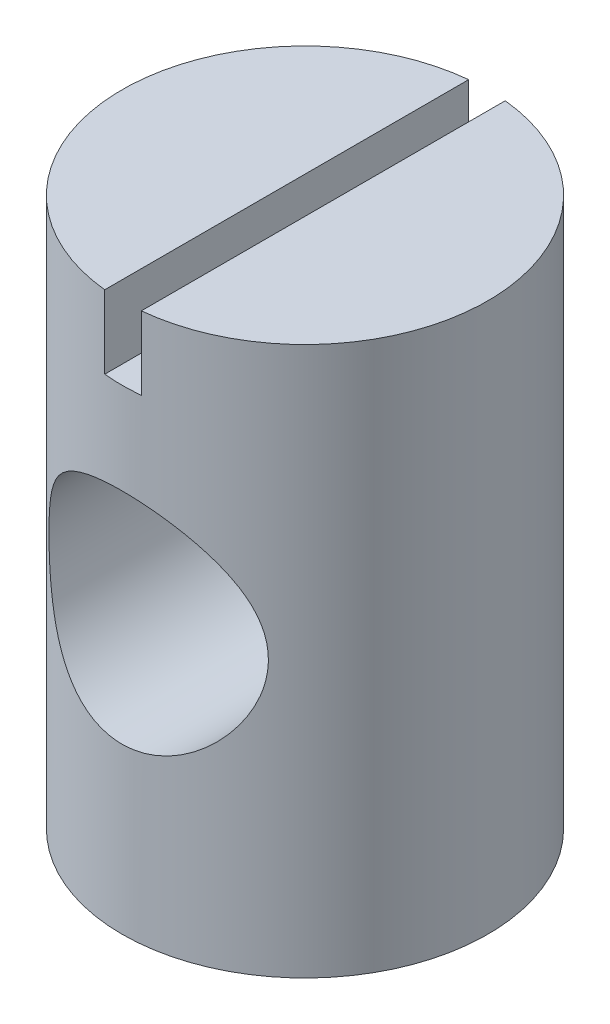
SolidWorks part; units mm, degrees
material "Промышленная бронза, UNS C22000 (90-10 Бронза)"
ref_plane "Спереди" through (0, 0, 0) normal (0, 0, 1) x (1, 0, 0)
ref_plane "Сверху" through (0, 0, 0) normal (0, 1, 0) x (1, 0, 0)
ref_plane "Справа" through (0, 0, 0) normal (1, 0, 0) x (0, 0, -1)
sketch "Эскиз1" plane through (0, 0, 0) normal (0, 1, 0) x (1, 0, 0)
  circle A0 centre (0, 0) radius 5
extrude "Бобышка-Вытянуть1" add sketch "Эскиз1" along normal blind 15
sketch "Эскиз2" plane through (0, 15, 0) normal (0, 1, 0) x (1, 0, 0)
  line L0 (0, 0) -> (0, 5.3321) construction
  line L2 (-0.5, 5) -> (0.5, 5)
  line L3 (-0.5, 5) -> (-0.5, -5)
  line L4 (-0.5, -5) -> (0.5, -5)
  line L5 (0.5, 5) -> (0.5, -5)
  dimension "D1" = 1
  dimension "D2" = 0.5
  dimension "D3" = 10
  dimension "D4" = 5
extrude "Вырез-Вытянуть1" cut sketch "Эскиз2" against normal blind 2
sketch "Эскиз3" plane through (0, 0, 0) normal (0, 0, 1) x (1, 0, 0)
  line L0 (0, 13) -> (0, -0.9669) construction
  line L1 (0.5, 13) -> (-0.5, 13) construction
  circle A0 centre (0, 7.5) radius 3
  dimension "D1" = 6
  dimension "D2" = 7.5
extrude "Вырез-Вытянуть2" cut sketch "Эскиз3" against normal blind 5 and the other way blind 5
